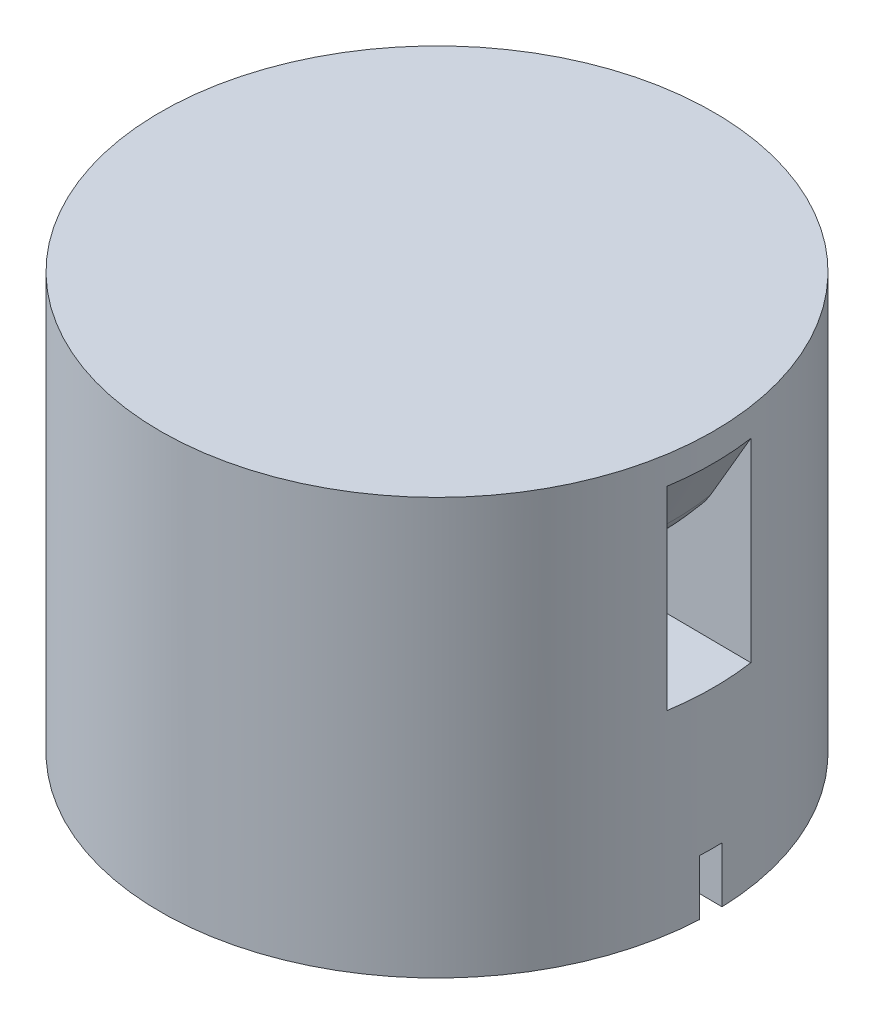
SolidWorks part; units mm, degrees
ref_plane "Front Plane" through (0, 0, 0) normal (0, 0, 1) x (1, 0, 0)
ref_plane "Top Plane" through (0, 0, 0) normal (0, 1, 0) x (1, 0, 0)
ref_plane "Right Plane" through (0, 0, 0) normal (1, 0, 0) x (0, 0, -1)
sketch "Sketch4" plane through (0, 0, 0) normal (0, 1, 0) x (1, 0, 0)
  circle A0 centre (-20.5796, -33.8554) radius 12.6543
extrude "Boss-Extrude3" add sketch "Sketch4" along normal blind 19.05
sketch "Sketch5" plane through (0, 19.05, 0) normal (0, 1, 0) x (1, 0, 0)
  line L0 (-10.0887, -40.9316) -> (-20.5796, -33.8554)
  line L1 (-20.5796, -33.8554) -> (-20.5796, -46.5097)
  circle A1 centre (-20.5796, -33.8554) radius 12.6543 construction
  dimension "D1" = 12.6543
  dimension "D2" = 12.6543
  dimension "D3" = 56
ref_plane "Plane6" through (0, 0, 46.5097) normal (0, 0, 1) x (1, 0, 0)
sketch "Sketch6" plane through (0, 0, 46.5097) normal (0, 0, 1) x (1, 0, 0)
  line L1 (-22.4389, 12.7) -> (-18.6289, 12.7)
  line L2 (-22.4389, 12.7) -> (-22.4389, 8.89)
  line L3 (-22.4389, 8.89) -> (-18.6289, 8.89)
  line L4 (-18.6289, 12.7) -> (-18.6289, 8.89)
  line L7 (-7.9253, 19.05) -> (-33.2339, 19.05) construction
  dimension "D1" = 3.81
  dimension "D4" = 6.35
sketch "Sketch8" plane through (0, 19.05, 0) normal (0, 1, 0) x (1, 0, 0)
  line L0 (-20.5796, -33.8554) -> (-33.2339, -33.8554)
  line L1 (-33.2339, -33.8554) -> (-7.9253, -33.8554)
  circle A0 centre (-20.5796, -33.8554) radius 12.6543 construction
extrude "Cut-Extrude5" cut sketch "Sketch6" against normal blind 5.08 contours L1 L4 L3 L2
chamfer "Chamfer4" distance 5.08 angle 30 1 edges at (-20.5334, 12.7, 46.5096) first distance on face at (-20.5796, 0, 46.5097)
fillet "Fillet1" radius 3.81 1 edges at (-20.533, 12.7, 43.5766)
pattern_circular "CirPattern1" count 2 over 360 about axis through (-20.5796, 19.05, 33.8554) along (0, -1, 0) of "Cut-Extrude5"
chamfer "Chamfer5" distance 5.08 angle 30 1 edges at (-20.6258, 12.7, 21.2011) first distance on face at (-20.5337, 13.335, 46.4375)
fillet "Fillet2" radius 3.81 1 edges at (-20.6262, 12.7, 24.1341)
scale "Scale2" scale about centroid uniform scaling yes scale factor 0.5
sketch "Sketch9" plane through (0, 4.7367, 0) normal (0, -1, 0) x (-1, 0, 0)
  line L2 (20.8336, -25.6021) -> (20.3256, -25.6021)
  line L3 (20.8336, -25.6021) -> (20.8336, -42.1086)
  line L4 (20.8336, -42.1086) -> (20.3256, -42.1086)
  line L5 (20.3256, -25.6021) -> (20.3256, -42.1086)
  line L6 (20.5796, -42.1086) -> (20.5796, -25.6021) construction
  line L7 (20.8336, -33.8554) -> (20.3256, -33.8554) construction
  point P0 (20.5796, -33.8554)
  dimension "D1" = 0.508
extrude "Cut-Extrude6" cut sketch "Sketch9" against normal blind 1.27
move or copy body "Body-Move/Copy1" bodies to move or copy 113 copy no rotation origin (-20.5796, 0, 33.8554) rotation axis (0, 1, 0) rotation angle 89.5
